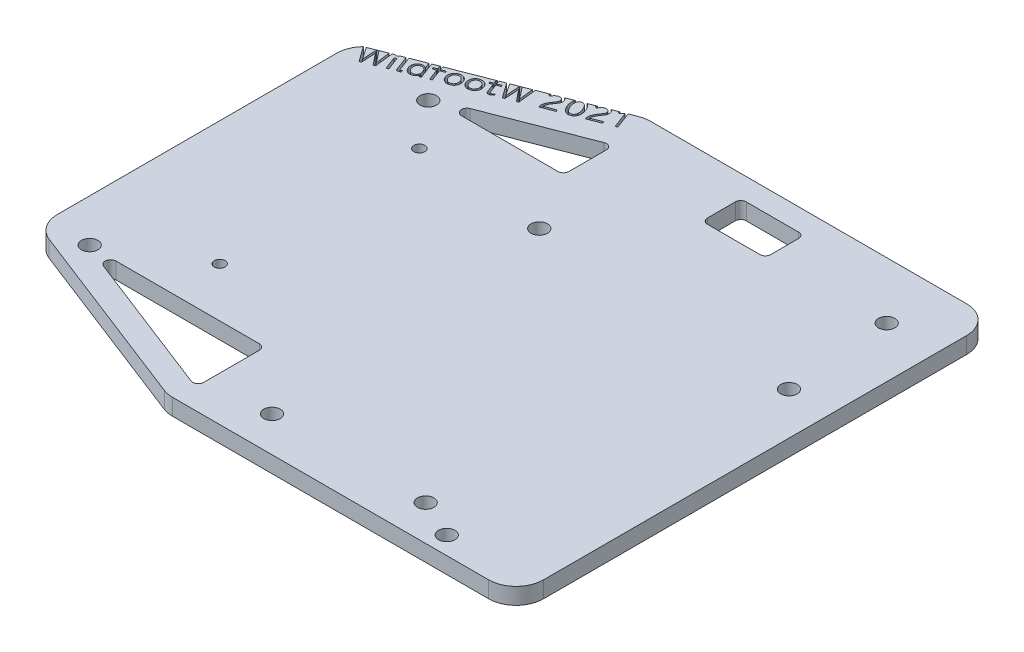
SolidWorks part; units mm, degrees
ref_plane "Front Plane" through (0, 0, 0) normal (0, 0, 1) x (1, 0, 0)
ref_plane "Top Plane" through (0, 0, 0) normal (0, 1, 0) x (1, 0, 0)
ref_plane "Right Plane" through (0, 0, 0) normal (1, 0, 0) x (0, 0, -1)
ref_plane "Plane1" through (0, 33, 0) normal (0, 1, 0) x (1, 0, 0)
sketch "Sketch1" plane through (0, 33, 0) normal (0, 1, 0) x (1, 0, 0)
  line L1 (0.59, -43.5583) -> (102.551, -43.5583)
  line L2 (0.59, -43.5583) -> (0.59, 43.5583)
  line L3 (0.59, 43.5583) -> (102.551, 43.5583)
  line L4 (102.551, -43.5583) -> (102.551, 43.5583)
  line L6 (0.59, 28.6267) -> (38.9977, 43.5583)
  line L8 (0.59, 28.6267) -> (38.9977, 28.6267) construction
  line L9 (38.9977, 28.6267) -> (38.9977, 43.5583) construction
  line L10 (6.0167, 0) -> (0.59, 0) construction
  line L11 (6.0167, 23.2) -> (6.0167, -23.2) construction
  line L12 (38.9977, 28.6267) -> (38.9977, 23.2) construction
  line L13 (40.3167, 23.2) -> (6.0167, 23.2) construction
  line L14 (38.9977, 28.6267) -> (44.4243, 28.6267) construction
  line L15 (44.4243, 28.4878) -> (44.4243, -37.1122) construction
  line L16 (0.59, -28.6267) -> (38.9977, -43.5583)
  line L17 (102.551, 0) -> (97.1243, 0) construction
  line L19 (97.1243, -37.1122) -> (97.1243, 28.4878) construction
  point P6 (0.59, 0)
extrude "Boss-Extrude1" add sketch "Sketch1" along normal blind 3 contours L2 L1 L4 L3 region at (54.2056, 33, 0)
sketch "Sketch2" plane through (0, 33, 0) normal (0, -1, 0) x (1, 0, 0)
  line L1 (3.0097, -26.2413) -> (36.7372, -39.3535) construction
  line L2 (0.59, -28.6267) -> (38.9977, -43.5583) construction
  text T0 "WildfootW 2021" font "@BIZ UDPGothic" height 3.5
  dimension "D1" = 3.1
extrude "Cut-Extrude1" cut sketch "Sketch2" against normal up to surface (3 mm away) up to face at (47.3796, 36, 0)
sketch "Sketch3" plane through (0, 33, 0) normal (0, 1, 0) x (1, 0, 0)
  line L0 (16.5148, 27.2) -> (40.4243, 36.4952)
  line L1 (40.4243, 36.4952) -> (40.4243, 27.2)
  line L2 (40.4243, 27.2) -> (16.5148, 27.2)
  line L3 (3.0097, 26.2413) -> (36.7372, 39.3535) construction
  line L4 (7.9594, -27.2) -> (40.4243, -27.2)
  line L5 (40.4243, -27.2) -> (40.4243, -39.8213)
  line L6 (40.4243, -39.8213) -> (7.9594, -27.2)
  line L7 (0.59, -28.6267) -> (38.9977, -43.5583) construction
  line L8 (40.4243, -27.2) -> (40.4243, -23.2) construction
  line L9 (44.4243, 28.4878) -> (44.4243, -37.1122) construction
  line L10 (44.4243, -27.2) -> (40.4243, -27.2) construction
  line L11 (6.0167, -23.2) -> (40.3167, -23.2) construction
  line L12 (24.1919, -33.5106) -> (22.7425, -37.2388) construction
  line L13 (40.4243, 27.2) -> (40.4243, 23.2) construction
  line L14 (40.3167, 23.2) -> (6.0167, 23.2) construction
  line L15 (40.4243, 27.2) -> (44.4243, 27.2) construction
  line L16 (28.4696, 31.8476) -> (27.0202, 35.5758) construction
  line L17 (56.4243, 31.8878) -> (60.3791, 32.4878) construction
  line L18 (60.3791, 32.4878) -> (71.9243, 32.4878)
  line L19 (60.3791, 32.4878) -> (60.3791, 39.5583)
  line L20 (60.3791, 39.5583) -> (71.9243, 39.5583)
  line L21 (71.9243, 32.4878) -> (71.9243, 39.5583)
  line L22 (60.3791, 32.4878) -> (60.3791, 28.4878) construction
  line L23 (75.9243, 28.4878) -> (56.4243, 28.4878) construction
  line L24 (71.9243, 32.4878) -> (75.9243, 32.4878) construction
  line L25 (75.9243, 35.7878) -> (75.9243, 19.1878) construction
  line L26 (71.9243, 39.5583) -> (71.9243, 43.5583) construction
  line L27 (38.9977, 43.5583) -> (102.551, 43.5583) construction
  dimension "D1" = 4
extrude "Cut-Extrude2" cut sketch "Sketch3" along normal up to surface (3 mm away) up to face at (22.3045, 36, -33.601)
fillet "Fillet1" radius 5 6 edges at (102.551, 34.5, 43.5583) (38.9977, 34.5, 43.5583) (0.59, 34.5, 28.6267) (0.59, 34.5, -28.6267) (38.9977, 34.5, -43.5583) (102.551, 34.5, -43.5583)
fillet "Fillet2" radius 1 10 edges at (60.3791, 34.5, -39.5583) (71.9243, 34.5, -39.5583) (40.4243, 34.5, -36.4952) (16.5148, 34.5, -27.2) (60.3791, 34.5, -32.4878) (71.9243, 34.5, -32.4878) (40.4243, 34.5, -27.2) (40.4243, 34.5, 39.8213) (40.4243, 34.5, 27.2) (7.9594, 34.5, 27.2)
sketch "Sketch4" plane through (0, 33, 0) normal (0, 1, 0) x (1, 0, 0)
  circle A0 centre (8.3674, -27.0854) radius 1.5
  circle A1 centre (86.6598, -40.308) radius 1.5
  circle A2 centre (93.3054, 33.2195) radius 1.5
  circle A3 centre (16.3794, 26.6064) radius 1.5
  circle A4 centre (16.3794, 26.6064) radius 1.5 construction
  circle A5 centre (93.3054, 33.2195) radius 1.5 construction
  circle A6 centre (86.6598, -40.308) radius 1.5 construction
  circle A7 centre (8.3674, -27.0854) radius 1.5 construction
  circle A8 centre (23.1667, -18.2) radius 1
  circle A9 centre (23.1667, 18.2) radius 1
  circle A10 centre (94.8243, 13.8878) radius 1.5
  circle A11 centre (46.7243, 16.4878) radius 1.5
  circle A12 centre (51.6243, -37.1122) radius 1.5
  circle A13 centre (79.6243, -37.1122) radius 1.5
  circle A14 centre (79.6243, -37.1122) radius 1.5 construction
  circle A15 centre (51.6243, -37.1122) radius 1.5 construction
  circle A16 centre (23.1667, -18.2) radius 1 construction
  circle A17 centre (23.1667, 18.2) radius 1 construction
  arc A18 (47.4243, 17.8144) -> (47.6243, 17.6878) centre (46.7243, 16.4878) ccw construction
  circle A19 centre (94.8243, 13.8878) radius 1.5 construction
extrude "Cut-Extrude3" cut sketch "Sketch4" along normal up to surface (3 mm away) up to face at (23.4446, 36, -32.2467)
